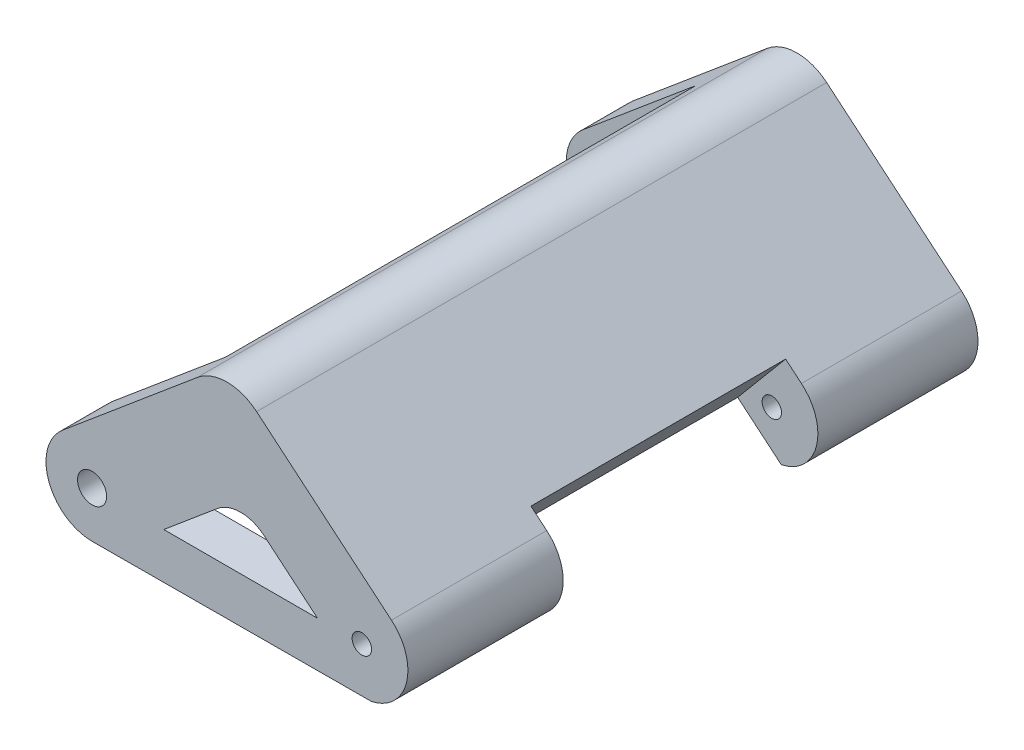
SolidWorks part; units mm, degrees
ref_plane "前视基准面" through (0, 0, 0) normal (0, 0, 1) x (1, 0, 0)
ref_plane "上视基准面" through (0, 0, 0) normal (0, 1, 0) x (1, 0, 0)
ref_plane "右视基准面" through (0, 0, 0) normal (1, 0, 0) x (0, 0, -1)
other "Configuration Table"
sketch "草图1" plane through (0, 0, 0) normal (0, 0, 1) x (1, 0, 0)
  line L0 (0, 0) -> (22.24, 0) construction
  line L1 (0, 3.8) -> (22.24, 3.8)
  line L2 (0, -3.8) -> (22.24, -3.8)
  line L3 (0, 0) -> (11.12, 9.3308) construction
  line L4 (-2.4426, 2.911) -> (8.6774, 12.2418)
  line L5 (2.4426, -2.911) -> (13.5626, 6.4198)
  line L6 (11.12, 9.3308) -> (22.24, 0) construction
  line L7 (13.5626, 12.2418) -> (24.6826, 2.911)
  line L8 (8.6774, 6.4198) -> (19.7974, -2.911)
  arc A0 (0, 3.8) -> (0, -3.8) centre (0, 0) ccw
  arc A1 (22.24, -3.8) -> (22.24, 3.8) centre (22.24, 0) ccw
  circle A2 centre (0, 0) radius 1.2
  circle A3 centre (22.24, 0) radius 0.8
  arc A4 (-2.4426, 2.911) -> (2.4426, -2.911) centre (0, 0) ccw
  arc A5 (13.5626, 6.4198) -> (8.6774, 12.2418) centre (11.12, 9.3308) ccw
  arc A6 (13.5626, 12.2418) -> (8.6774, 6.4198) centre (11.12, 9.3308) ccw
  arc A7 (19.7974, -2.911) -> (24.6826, 2.911) centre (22.24, 0) ccw
  point P3 (11.12, 0)
  point P12 (5.56, 4.6654)
  point P18 (16.68, 4.6654)
  dimension "D1" = 2.4
  dimension "D2" = 3.8
  dimension "D4" = 1.6
  dimension "D3" = 22.24
  dimension "D5" = 100
extrude "凸台-拉伸3" add sketch "草图1" along normal blind 47 contours A6 L4 A0 L1 L5 L8 | A0 A4 L5 L1 A2 | A5 A6 L8 L5 | A5 L5 L8 L1 A1 L7 | L8 A7 A1 L1 A3 region at (5.2974, 6.0641, 0) region at (1.9391, 0.7058, 0) region at (16.9426, 6.0641, 0) region at (20.3754, 0.6787, 0) region at (11.12, 9.1561, 0)
sketch "草图6" plane through (11.6316, 13.862, 0) normal (0.6428, 0.766, 0) x (0.766, -0.6428, 0)
  line L0 (20.8368, -47) -> (20.8368, 0) construction
  line L1 (15.3368, -13.2) -> (20.8368, -13.2)
  line L2 (15.3368, -13.2) -> (15.3368, -34.2)
  line L3 (15.3368, -34.2) -> (20.8368, -34.2)
  line L4 (20.8368, -13.2) -> (20.8368, -34.2)
  line L5 (15.3368, -13.2) -> (20.8368, -34.2) construction
  line L6 (15.3368, -34.2) -> (20.8368, -13.2) construction
  line L7 (2.5207, -47) -> (17.0368, -47) construction
  point P0 (18.0868, -23.7)
  dimension "D1" = 5.5
  dimension "D2" = 21
  dimension "D3" = 12.8
extrude "切除-拉伸4" cut sketch "草图6" against normal through all
sketch "草图7" plane through (-2.4426, 2.911, 0) normal (-0.6428, 0.766, 0) x (0.766, 0.6428, 0)
  line L0 (0, -23.5) -> (50000, -23.5) construction
  line L1 (0, -47) -> (0, 0) construction
  line L2 (-3.8, 0) -> (-3.8, -47) construction
  line L3 (11.2, -4.1) -> (-3.8, -4.1)
  line L4 (11.2, -4.1) -> (11.2, -42.9)
  line L5 (11.2, -42.9) -> (-3.8, -42.9)
  line L6 (-3.8, -4.1) -> (-3.8, -42.9)
  line L7 (11.2, -4.1) -> (-3.8, -42.9) construction
  line L8 (11.2, -42.9) -> (-3.8, -4.1) construction
  point P4 (0, -23.5)
  point P5 (3.7, -23.5)
  dimension "D1" = 15
  dimension "D2" = 19.4
extrude "切除-拉伸5" cut sketch "草图7" against normal through all
sketch "草图8" plane through (0, 0, 47) normal (0, 0, 1) x (1, 0, 0)
  line L0 (19.0314, -2.2682) -> (23.0185, -3.7194)
  line L1 (11.12, 4.3702) -> (19.7974, -2.911) construction
  line L2 (19.0314, -2.2682) -> (19.7974, -2.911)
  arc A0 (19.7974, -2.911) -> (24.6826, 2.911) centre (22.24, 0) ccw construction
  arc A1 (23.0185, -3.7194) -> (19.7974, -2.911) centre (22.24, 0) cw
  dimension "D1" = 160
  dimension "D2" = 1
extrude "切除-拉伸6" cut sketch "草图8" against normal through all
sketch "草图9" plane through (0, 0, 47) normal (0, 0, 1) x (1, 0, 0)
  line L0 (23.0185, -3.7194) -> (12.2488, 5.3175)
  line L1 (12.2488, 5.3175) -> (11.12, 4.3702)
  line L2 (11.12, 4.3702) -> (19.0314, -2.2682)
  line L3 (19.0314, -2.2682) -> (23.0185, -3.7194)
  line L4 (2.4426, -2.911) -> (11.12, 4.3702) construction
extrude "切除-拉伸7" cut sketch "草图9" against normal through all
sketch "草图10" plane through (8.5797, 7.1992, 0) normal (-0.766, -0.6428, 0) x (0, 0, 1)
  line L1 (4.1, 3.8) -> (42.9, 3.8)
  line L2 (4.1, 3.8) -> (4.1, -3.8)
  line L3 (4.1, -3.8) -> (42.9, -3.8)
  line L4 (42.9, 3.8) -> (42.9, -3.8)
extrude "切除-拉伸8" cut sketch "草图10" against normal blind 1
sketch "草图11" plane through (0, 0, 47) normal (0, 0, 1) x (1, 0, 0)
  line L0 (0.0133, -3.8) -> (23.0185, -3.7194)
  line L1 (23.0185, -3.7194) -> (18.5859, 0)
  line L2 (23.0185, -3.7194) -> (12.2488, 5.3175) construction
  line L3 (18.5859, 0) -> (5.9118, 0)
  line L4 (2.4426, -2.911) -> (12.2488, 5.3175) construction
  line L5 (5.9118, 0) -> (0.0133, -3.8)
  arc A0 (-2.4426, 2.911) -> (2.4426, -2.911) centre (0, 0) ccw construction
extrude "凸台-拉伸4" add sketch "草图11" against normal blind 3.5
ref_plane "基准面2" through (0, 0, 23.5) normal (0, 0, -1) x (-1, 0, 0)
mirror "镜向2" about plane through (0, 0, 23.5) normal (0, 0, -1) of "凸台-拉伸4"
fillet "圆角1" radius 3 1 edges at (12.2488, 5.3175, 23.5)
sketch "草图12" plane through (0, 0, 4.1) normal (0, 0, 1) x (1, 0, 0)
  line L0 (0.0133, -3.8) -> (23.0185, -3.7194) construction
  circle A0 centre (5.5, -3.7808) radius 3.5
  circle A1 centre (0, 0) radius 1.2 construction
  dimension "D1" = 7
  dimension "D2" = 5.5
extrude "切除-拉伸9" cut sketch "草图12" against normal blind 2
